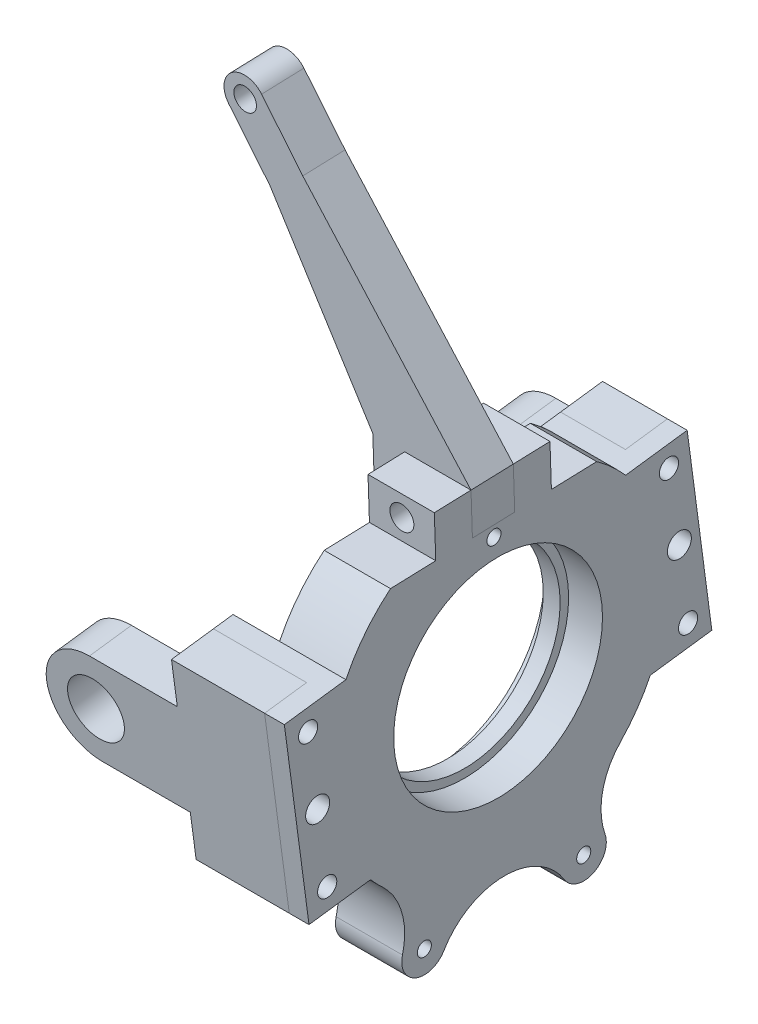
SolidWorks part; units mm, degrees
note: The reader was unsure of these and kept them because the rebuilt part matched: shared geometry of "Sketch23<2>", "Sketch23<3>", "Sketch26<4>", "Sketch2<2>".
ref_plane "Front Plane" through (0, 0, 0) normal (1, 0, 0) x (0, 1, 0)
ref_plane "Top Plane" through (0, 0, 0) normal (0, 0, 1) x (0, 1, 0)
ref_plane "Right Plane" through (0, 0, 0) normal (0, 1, 0) x (-1, 0, 0)
sketch3d "3DSketch"
  line L19 (600, -2.549, 292.0889) -> (600, 0, 0)
  line L20 (600, -2.549, 292.0889) -> (460, -2.549, 292.0889)
  line L21 (442.763, 142.8106, 296.9835) -> (460, -2.549, 292.0889)
  line L22 (274.4002, 153.4499, 364.0529) -> (442.763, 142.8106, 296.9835)
  line L23 (358.74, -21.3348, 955.1942) -> (374, -15.2698, 454.8841)
  line L24 (257, 140.0361, 313.934) -> (257, -131.4609, 311.5647)
  line L25 (448.877, -13.1797, 372.1042) -> (471.393, 8.0816, 212.0736)
  line L26 (257, 153.7979, 459.0125) -> (448.877, -13.1797, 372.1042)
  line L27 (257, -142.4803, 454.9242) -> (448.877, -13.1797, 372.1042)
  line L28 (257, 153.7979, 459.0125) -> (257, -142.4803, 454.9242)
  line L29 (288.9278, -123.0576, 447.6519) -> (291.5458, 111.2203, 447.5991)
  line L30 (290.2593, -3.9064, 447.625) -> (290.2593, 0, 0)
  line L31 (245.1032, -5.7853, 662.9327) -> (245.1032, 0, 0)
  line L32 (290.2593, -3.9064, 447.625) -> (245.1032, -5.7853, 662.9327)
  line L33 (257, -131.4609, 311.5647) -> (471.393, 8.0816, 212.0736)
  line L34 (257, 140.0361, 313.934) -> (471.393, 8.0816, 212.0736)
  line L35 (600, 0, 0) -> (-600, 0, 0)
  line L36 (0, 0, 0) -> (0, -1300, 0)
  line L37 (-625, -1300, 0) -> (625, -1300, 0)
ref_plane "Plane1" through (600, -2.549, 292.0889) normal (-1, 0, 0) x (0, 0, 1)
ref_plane "Plane2" through (520, -2.549, 292.0889) normal (-1, 0, 0) x (0, 0, 1)
sketch "Sketch1" plane through (520, -2.549, 292.0889) normal (-1, 0, 0) x (0, 0, 1)
  line L0 (4.8947, 145.3596) -> (0, 0) construction
  line L1 (4.8947, 145.3596) -> (0, 0) construction
  line L2 (38.1286, 46.3272) -> (-34.9258, 48.7872) construction
  line L4 (22.0898, 46.8673) -> (22.5946, 61.8588)
  line L5 (22.5946, 61.8588) -> (9.6019, 62.2963)
  line L6 (9.6019, 62.2963) -> (9.0971, 47.3048)
  line L8 (-5.8944, 47.8096) -> (-5.3896, 62.8011)
  line L9 (-5.3896, 62.8011) -> (-18.3822, 63.2386)
  line L10 (-18.3822, 63.2386) -> (-18.887, 48.2471)
  line L12 (-18.887, 48.2471) -> (22.0898, 46.8673) construction
  line L13 (80.0153, -10.6307) -> (-80.0153, 10.6307) construction
  line L14 (80.0153, -10.6307) -> (-80.0153, 10.6307) construction
  line L15 (53.9331, 26.291) -> (45.1974, -39.4613)
  line L16 (-53.9331, -26.291) -> (-45.1974, 39.4613)
  line L17 (-34.9258, 48.7872) -> (-18.887, 48.2471)
  line L18 (-5.8944, 47.8096) -> (9.0971, 47.3048)
  line L19 (22.0898, 46.8673) -> (38.1286, 46.3272)
  circle A0 centre (0, 0) radius 40 construction
  circle A1 centre (0, 0) radius 60 construction
  circle A2 centre (-61.4765, -58.6996) radius 25 construction
  circle A3 centre (-30.346, -69.6491) radius 8 construction
  circle A4 centre (-2.2756, -87) radius 25 construction
  circle A5 centre (26.1397, -70.22) radius 8 construction
  circle A6 centre (58.1086, -62.0354) radius 25 construction
  arc A9 (-53.9331, -26.291) -> (-43.3952, -41.435) centre (0, 0) ccw
  arc A10 (-43.3952, -41.435) -> (-37.8928, -66.9947) centre (-61.4765, -58.6996) cw
  arc A11 (-37.8928, -66.9947) -> (-23.5411, -73.8554) centre (-30.346, -69.6491) ccw
  arc A12 (-23.5411, -73.8554) -> (19.2511, -74.2878) centre (-2.2756, -87) cw
  arc A13 (19.2511, -74.2878) -> (33.8897, -68.2358) centre (26.1397, -70.22) ccw
  arc A14 (33.8897, -68.2358) -> (41.0178, -43.7897) centre (58.1086, -62.0354) cw
  arc A15 (41.0178, -43.7897) -> (45.1974, -39.4613) centre (0, 0) ccw
  arc A16 (53.9331, 26.291) -> (38.1286, 46.3272) centre (0, 0) ccw
  arc A17 (-45.1974, 39.4613) -> (-34.9258, 48.7872) centre (0, 0) cw
  point P16 (2.0165, 59.884)
  point P24 (2.2614, 68.1431)
  point P33 (1.6014, 47.5572)
  point P35 (33.8897, -68.2358)
  dimension "D1" = 80
  dimension "D2" = 120
  dimension "D10" = 50
  dimension "D11" = 16
  dimension "D12" = 50
  dimension "D15" = 16
  dimension "D16" = 50
  dimension "D3" = 13
  dimension "D4" = 13
  dimension "D5" = 15
  dimension "D6" = 15
  dimension "D7" = 15
  dimension "D8" = 66.33
  dimension "D9" = 66.33
  dimension "D13" = 87
extrude "Boss-Extrude1" add sketch "Sketch1" along normal blind 23.5
sketch "Sketch2" plane through (520, 0, 0) normal (1, 0, 0) x (0, 1, 0)
  line L0 (37.4283, 293.435) -> (45.0082, 293.6903) construction
  line L1 (142.8106, 296.9835) -> (-2.549, 292.0889) construction
  line L2 (142.8106, 296.9835) -> (-2.549, 292.0889) construction
  line L3 (45.2606, 286.1945) -> (44.7558, 301.186) construction
  circle A0 centre (-2.549, 292.0889) radius 40 construction
  circle A1 centre (-2.549, 292.0889) radius 40
  circle A2 centre (-72.769, 318.2285) radius 8 construction
  circle A3 centre (-72.1981, 261.7429) radius 8 construction
  circle A4 centre (-72.769, 318.2285) radius 8 construction
  circle A5 centre (-72.1981, 261.7429) radius 8 construction
  circle A6 centre (-72.769, 318.2285) radius 2.5
  circle A7 centre (-72.1981, 261.7429) radius 2.5
  circle A8 centre (41.2183, 293.5626) radius 2.5
  point P12 (37.4283, 293.435)
  point P13 (45.0082, 293.6903)
  dimension "D1" = 5
  dimension "D2" = 5
  dimension "D3" = 5
extrude "Cut-Extrude3" cut sketch "Sketch2" against normal blind 54.5
sketch "Sketch3" plane through (0, -10.5171, 312.3322) normal (0, -0.0337, 0.9994) x (1, 0, 0)
  line L4 (520, 54.8665) -> (520, 69.8665)
  line L5 (520, 69.8665) -> (496.5, 69.8665)
  line L6 (496.5, 69.8665) -> (496.5, 54.8665)
  line L7 (496.5, 54.8665) -> (520, 54.8665)
  line L8 (520, 54.8665) -> (520, 69.8665) construction
  line L9 (520, 69.8665) -> (496.5, 69.8665) construction
  line L10 (496.5, 69.8665) -> (496.5, 54.8665) construction
  line L12 (496.5, 54.8665) -> (520, 54.8665)
  circle A1 centre (508.25, 62.3665) radius 4.25
  dimension "D2" = 8.5
  dimension "D1" = 0
extrude "Cut-Extrude4" cut sketch "Sketch3" against normal blind 54.5 contours A1
sketch "Sketch5" plane through (0, -31.5923, 237.7901) normal (0, 0.1317, -0.9913) x (1, 0, 0)
  line L1 (520, -2.7765) -> (490, -2.7765)
  line L2 (520, -2.7765) -> (520, -69.1065)
  line L3 (520, -69.1065) -> (490, -69.1065)
  line L4 (520, -69.1065) -> (520, -2.7765)
  line L5 (520, -2.7765) -> (496.5, -2.7765)
  line L6 (496.5, -2.7765) -> (496.5, -69.1065)
  line L7 (496.5, -69.1065) -> (520, -69.1065)
  line L8 (520, -69.1065) -> (520, -2.7765) construction
  line L9 (520, -2.7765) -> (496.5, -2.7765) construction
  line L10 (496.5, -2.7765) -> (496.5, -69.1065) construction
  line L11 (496.5, -69.1065) -> (520, -69.1065) construction
  line L12 (490, -2.7765) -> (490, -69.1065)
  dimension "D2" = 30
  dimension "D1" = 0
extrude "Boss-Extrude2" add sketch "Sketch5" along normal blind 7
sketch "Sketch8" plane through (0, -30.6704, 230.851) normal (0, 0.1317, -0.9913) x (1, 0, 0)
  line L1 (520, -2.7765) -> (513, -2.7765)
  line L2 (520, -2.7765) -> (520, -69.1065)
  line L3 (520, -69.1065) -> (513, -69.1065)
  line L4 (490, -69.1065) -> (520, -69.1065)
  line L5 (520, -69.1065) -> (520, -2.7765)
  line L6 (520, -2.7765) -> (490, -2.7765)
  line L7 (490, -2.7765) -> (490, -69.1065)
  line L8 (490, -69.1065) -> (520, -69.1065) construction
  line L9 (520, -69.1065) -> (520, -2.7765) construction
  line L10 (520, -2.7765) -> (490, -2.7765) construction
  line L11 (490, -2.7765) -> (490, -69.1065) construction
  line L12 (513, -2.7765) -> (513, -69.1065)
  dimension "D2" = 7
  dimension "D1" = 0
extrude "Boss-Extrude4" add sketch "Sketch8" along normal blind 15
sketch "Sketch9" plane through (513, 0, 0) normal (-1, 0, 0) x (0, -1, 0)
  line L0 (-6.9335, 220.7152) -> (-4.958, 235.5846) construction
  line L1 (-22.9648, 237.9769) -> (-24.9403, 223.1076) construction
  line L2 (-37.8341, 239.9524) -> (-22.9648, 237.9769) construction
  line L4 (27.9181, 231.2167) -> (-37.8341, 239.9524)
  line L5 (-37.8341, 239.9524) -> (-39.8097, 225.0831)
  line L6 (-39.8097, 225.0831) -> (25.9426, 216.3474)
  line L7 (25.9426, 216.3474) -> (27.9181, 231.2167)
  line L8 (27.9181, 231.2167) -> (-37.8341, 239.9524) construction
  line L9 (-37.8341, 239.9524) -> (-39.8097, 225.0831) construction
  line L10 (-39.8097, 225.0831) -> (25.9426, 216.3474) construction
  line L11 (25.9426, 216.3474) -> (27.9181, 231.2167) construction
  circle A0 centre (-31.3872, 231.53) radius 3.4
  circle A1 centre (-5.9857, 227.8493) radius 4.25
  circle A2 centre (19.4957, 224.7698) radius 3.4
  dimension "D2" = 6.8
  dimension "D3" = 8.5
  dimension "D1" = 0
extrude "Cut-Extrude7" cut sketch "Sketch9" against normal blind 15
sketch "Sketch13" plane through (0, -44.7626, 336.9207) normal (0, -0.1317, 0.9913) x (1, 0, 0)
  line L1 (520, 69.1065) -> (480, 69.1065)
  line L2 (520, 69.1065) -> (520, 2.7765)
  line L3 (520, 2.7765) -> (480, 2.7765)
  line L4 (496.5, 2.7765) -> (520, 2.7765)
  line L5 (520, 2.7765) -> (520, 69.1065)
  line L6 (520, 69.1065) -> (496.5, 69.1065)
  line L7 (496.5, 69.1065) -> (496.5, 2.7765)
  line L8 (496.5, 2.7765) -> (520, 2.7765) construction
  line L9 (520, 2.7765) -> (520, 69.1065) construction
  line L10 (520, 69.1065) -> (496.5, 69.1065) construction
  line L11 (496.5, 69.1065) -> (496.5, 2.7765) construction
  line L12 (480, 69.1065) -> (480, 2.7765)
  dimension "D2" = 40
  dimension "D1" = 0
extrude "Boss-Extrude9" add sketch "Sketch13" along normal blind 7
sketch "Sketch16" plane through (0, -45.6845, 343.8597) normal (0, -0.1317, 0.9913) x (1, 0, 0)
  line L0 (520, 79.7039) -> (520, 69.1065) construction
  line L1 (520, 69.1065) -> (513, 69.1065)
  line L2 (520, 69.1065) -> (520, 2.7765)
  line L3 (520, 2.7765) -> (513, 2.7765)
  line L4 (513, 69.1065) -> (513, 2.7765)
  line L5 (520, 2.7765) -> (520, 69.1065) construction
  line L6 (496.5, 2.7765) -> (520, 2.7765) construction
  line L9 (496.5, 69.1065) -> (520, 69.1065) construction
  line L10 (520, 2.7765) -> (480, 2.7765) construction
  dimension "D1" = 7
extrude "Boss-Extrude10" add sketch "Sketch16" along normal blind 15
sketch "Sketch18" plane through (513, 0, 0) normal (-1, 0, 0) x (0, -1, 0)
  line L0 (-7.9507, 350.9855) -> (-5.9752, 365.8549) construction
  line L1 (-5.9752, 365.8549) -> (-20.8445, 367.8304) construction
  line L2 (12.0316, 363.4625) -> (10.0561, 348.5932) construction
  line L4 (-22.8201, 352.9611) -> (42.9322, 344.2254)
  line L5 (42.9322, 344.2254) -> (44.9077, 359.0947)
  line L6 (44.9077, 359.0947) -> (-20.8445, 367.8304)
  line L7 (-20.8445, 367.8304) -> (-22.8201, 352.9611)
  line L8 (-22.8201, 352.9611) -> (42.9322, 344.2254) construction
  line L9 (42.9322, 344.2254) -> (44.9077, 359.0947) construction
  line L10 (44.9077, 359.0947) -> (-20.8445, 367.8304) construction
  line L11 (-20.8445, 367.8304) -> (-22.8201, 352.9611) construction
  circle A0 centre (-14.3976, 359.408) radius 3.4
  circle A1 centre (11.0438, 356.0279) radius 4.25
  circle A2 centre (36.4853, 352.6478) radius 3.4
  dimension "D2" = 6.8
  dimension "D3" = 8.5
  dimension "D1" = 0
extrude "Cut-Extrude10" cut sketch "Sketch18" against normal blind 15
ref_plane "Plane3" through (508, -2.549, 292.0889) normal (-1, 0, 0) x (0, 0, 1)
sketch "Sketch19" plane through (508, -2.549, 292.0889) normal (-1, 0, 0) x (0, 0, 1)
  circle A0 centre (0, 0) radius 34
  circle A1 centre (0, 0) radius 40 construction
  circle A2 centre (0, 0) radius 40
  dimension "D1" = 68
extrude "Boss-Extrude11" add sketch "Sketch19" along normal blind 6
sketch "Sketch20" plane through (508, 0, 0) normal (1, 0, 0) x (0, 1, 0)
  circle A0 centre (-2.549, 292.0889) radius 40 construction
  circle A1 centre (-2.549, 292.0889) radius 40
  circle A2 centre (-2.549, 292.0889) radius 37
  dimension "D1" = 74
extrude "Boss-Extrude12" add sketch "Sketch20" along direction (1, 0, 0) on the side of the normal up to surface (12 mm away) up to face at (520, 14.3976, 356.008)
sketch "Sketch22" plane through (0, -45.6845, 343.8597) normal (0, -0.1317, 0.9913) x (1, 0, 0)
  line L0 (600, 35.9415) -> (460, 35.9415) construction
  line L1 (448.877, 18.4415) -> (480, 18.4415)
  line L2 (448.877, 18.4415) -> (448.877, 53.4415) construction
  line L3 (448.877, 53.4415) -> (480, 53.4415)
  line L4 (480, 2.7765) -> (513, 2.7765)
  line L5 (513, 2.7765) -> (513, 69.1065)
  line L6 (513, 69.1065) -> (480, 69.1065)
  line L7 (480, 69.1065) -> (480, 2.7765)
  line L8 (480, 2.7765) -> (513, 2.7765)
  line L9 (513, 2.7765) -> (513, 69.1065)
  line L10 (513, 69.1065) -> (480, 69.1065)
  line L11 (480, 69.1065) -> (480, 2.7765) construction
  line L12 (480, 18.4415) -> (480, 53.4415) construction
  line L13 (448.877, 18.4415) -> (480, 53.4415) construction
  line L14 (448.877, 53.4415) -> (480, 18.4415) construction
  line L15 (480, 69.1065) -> (480, 53.4415)
  line L16 (480, 18.4415) -> (480, 2.7765)
  arc A0 (448.877, 53.4415) -> (448.877, 18.4415) centre (448.877, 35.9415) ccw
  circle A1 centre (448.877, 35.9415) radius 10
  point P2 (448.877, 35.9415)
  point P4 (464.4385, 35.9415)
  dimension "D3" = 20
  dimension "D2" = 35
  dimension "D1" = 0
extrude "Boss-Extrude13" add sketch "Sketch22" along normal blind 15 separate body contours L8 L9 L10 L15 L3 A0 L1 L16 | A1
sketch "Sketch23" plane through (513, 0, 0) normal (1, 0, 0) x (0, 1, 0)
  line L0 (-44.9077, 359.0947) -> (-30.0384, 361.0702) construction
  line L1 (-30.0384, 361.0702) -> (-28.0628, 346.2009) construction
  line L2 (-12.0316, 363.4625) -> (-10.0561, 348.5932) construction
  line L4 (-42.9322, 344.2254) -> (22.8201, 352.9611)
  line L5 (22.8201, 352.9611) -> (20.8445, 367.8304)
  line L6 (20.8445, 367.8304) -> (-44.9077, 359.0947)
  line L7 (-44.9077, 359.0947) -> (-42.9322, 344.2254)
  line L8 (-42.9322, 344.2254) -> (22.8201, 352.9611) construction
  line L9 (22.8201, 352.9611) -> (20.8445, 367.8304) construction
  line L10 (20.8445, 367.8304) -> (-44.9077, 359.0947) construction
  line L11 (-44.9077, 359.0947) -> (-42.9322, 344.2254) construction
  circle A0 centre (-36.4853, 352.6478) radius 3.4
  circle A1 centre (-11.0438, 356.0279) radius 4.25
  circle A2 centre (14.3976, 359.408) radius 3.4
  dimension "D2" = 6.8
  dimension "D3" = 8.5
  dimension "D1" = 0
extrude "Cut-Extrude11" cut sketch "Sketch23" against normal blind 28
extrude "Cut-Extrude12" cut sketch "Sketch23<2>" against normal blind 62 contours A2
sketch "Sketch23<2>" plane through (513, 0, 0) normal (1, 0, 0) x (0, 1, 0) same geometry as "Sketch23"
extrude "Cut-Extrude13" cut sketch "Sketch23<3>" against normal blind 62 contours A0
sketch "Sketch23<3>" plane through (513, 0, 0) normal (1, 0, 0) x (0, 1, 0) same geometry as "Sketch23"
sketch "Sketch25" plane through (0, -30.6704, 230.851) normal (0, 0.1317, -0.9913) x (1, 0, 0)
  line L2 (448.877, -18.4415) -> (480, -18.4415) construction
  line L3 (448.877, -53.4415) -> (480, -53.4415) construction
  line L4 (490, -69.1065) -> (513, -69.1065)
  line L5 (513, -69.1065) -> (513, -2.7765)
  line L6 (513, -2.7765) -> (490, -2.7765)
  line L7 (490, -2.7765) -> (490, -69.1065)
  line L8 (490, -69.1065) -> (513, -69.1065)
  line L9 (513, -69.1065) -> (513, -2.7765)
  line L10 (513, -2.7765) -> (490, -2.7765)
  line L11 (490, -2.7765) -> (490, -69.1065) construction
  line L12 (471.393, -18.4415) -> (480, -18.4415)
  line L13 (471.393, -53.4415) -> (480, -53.4415)
  line L14 (490, -2.7765) -> (490, -18.4415)
  line L15 (490, -18.4415) -> (480, -18.4415)
  line L16 (480, -53.4415) -> (490, -53.4415)
  line L17 (490, -53.4415) -> (490, -69.1065)
  arc A0 (471.393, -18.4415) -> (471.393, -53.4415) centre (471.393, -35.9415) ccw
  circle A2 centre (471.393, -35.9415) radius 10
  point P2 (471.393, -35.9415)
  dimension "D2" = 20
  dimension "D1" = 0
extrude "Boss-Extrude14" add sketch "Sketch25" along normal blind 15 separate body
sketch "Sketch26" plane through (0, -9.5748, 284.348) normal (0, -0.0337, 0.9994) x (1, 0, 0)
  line L0 (496.5, 54.8665) -> (496.5, 47.7845)
  line L1 (496.5, 45.2002) -> (496.5, -20.8088) construction
  line L2 (496.5, 47.7845) -> (485.2018, 47.7845)
  line L3 (485.2018, 47.7845) -> (485.2018, 69.8665)
  line L4 (520, 54.8665) -> (520, 69.8665)
  line L5 (520, 69.8665) -> (496.5, 69.8665)
  line L6 (496.5, 69.8665) -> (496.5, 54.8665)
  line L7 (496.5, 54.8665) -> (520, 54.8665)
  line L8 (520, 54.8665) -> (520, 69.8665)
  line L9 (520, 69.8665) -> (496.5, 69.8665)
  line L11 (496.5, 54.8665) -> (520, 54.8665)
  line L13 (436.787, 148.1925) -> (450.7571, 129.7705)
  line L14 (450.7571, 129.7705) -> (462.7091, 138.8341) construction
  line L15 (462.7091, 138.8341) -> (448.739, 157.2561)
  line L16 (450.7571, 129.7705) -> (485.2018, 69.8665)
  line L17 (462.7091, 138.8341) -> (520, 69.8665)
  circle A0 centre (442.763, 152.7243) radius 7.5 construction
  circle A1 centre (442.763, 152.7243) radius 4
  arc A2 (436.787, 148.1925) -> (448.739, 157.2561) centre (442.763, 152.7243) cw
  point P17 (496.5, 47.7845)
  dimension "D2" = 15
  dimension "D3" = 8
  dimension "D1" = 0
extrude "Boss-Extrude15" add sketch "Sketch26" along normal blind 15 separate body contours L8 L11 L0 L2 L3 L16 L13 A2 L15 L17
extrude "Cut-Extrude15" cut sketch "Sketch26<4>" along normal blind 89 contours A1
sketch "Sketch26<4>" plane through (0, -9.5748, 284.348) normal (0, -0.0337, 0.9994) x (1, 0, 0) same geometry as "Sketch26"
extrude "Cut-Extrude16" cut sketch "Sketch2<2>" against normal blind 89 contours A8
sketch "Sketch2<2>" plane through (520, 0, 0) normal (1, 0, 0) x (0, 1, 0) same geometry as "Sketch2"
sketch "Sketch27" plane through (0, -10.0796, 299.3396) normal (0, -0.0337, 0.9994) x (1, 0, 0)
  circle A0 centre (508.25, 62.3665) radius 4.25 construction
  circle A1 centre (508.25, 62.3665) radius 4.25
extrude "Cut-Extrude17" cut sketch "Sketch27" against normal blind 36
